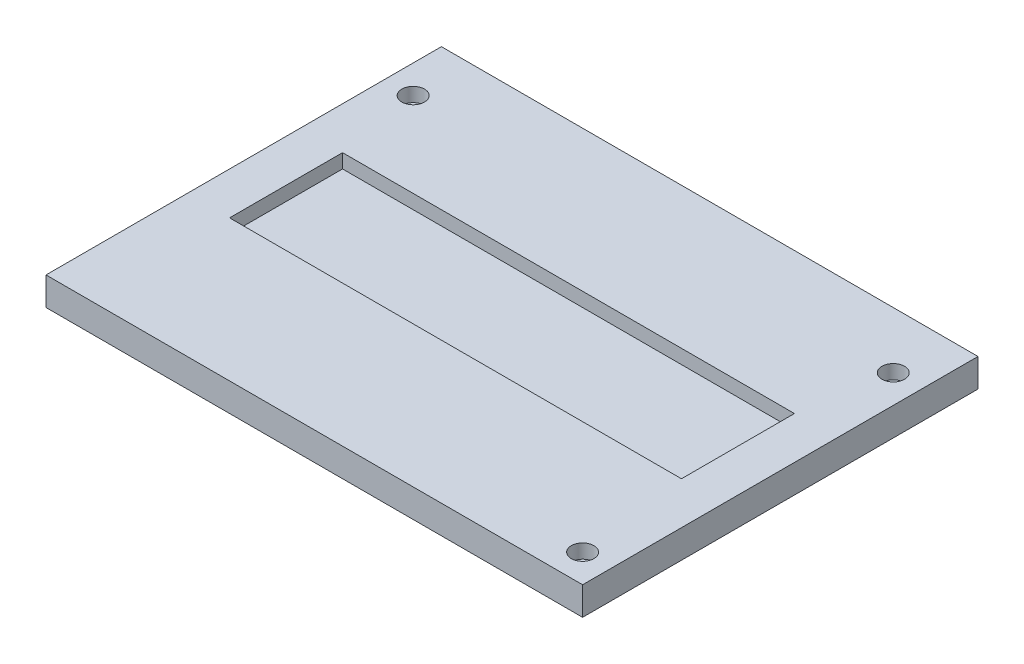
SolidWorks part; units mm, degrees
material "ABS"
ref_plane "Front" through (0, 0, 0) normal (0, 0, 1) x (1, 0, 0)
ref_plane "Top" through (0, 0, 0) normal (0, 1, 0) x (1, 0, 0)
ref_plane "Right" through (0, 0, 0) normal (1, 0, 0) x (0, 0, -1)
sketch "Sketch1" plane through (0, 0, 0) normal (0, 1, 0) x (1, 0, 0)
  line L1 (-60.325, 44.45) -> (60.325, 44.45)
  line L2 (-60.325, 44.45) -> (-60.325, -44.45)
  line L3 (-60.325, -44.45) -> (60.325, -44.45)
  line L4 (60.325, 44.45) -> (60.325, -44.45)
  line L5 (-60.325, 44.45) -> (60.325, -44.45) construction
  line L6 (-60.325, -44.45) -> (60.325, 44.45) construction
  point P0 (0, 0)
  dimension "D1" = 120.65
  dimension "D2" = 88.9
extrude "Boss-Extrude1" add sketch "Sketch1" along normal blind 6.35
sketch "Sketch7" plane through (0, 6.35, 0) normal (0, 1, 0) x (1, 0, 0)
  line L0 (60.325, 44.45) -> (-60.325, 44.45) construction
  line L1 (-60.325, 44.45) -> (-60.325, -44.45) construction
  line L2 (60.325, -44.45) -> (60.325, 44.45) construction
  line L3 (-60.325, -44.45) -> (60.325, -44.45) construction
  circle A0 centre (-53.975, 31.75) radius 2.54
  circle A1 centre (53.975, 31.75) radius 2.54
  circle A2 centre (53.975, -38.1) radius 2.54
  point P12 (0, 0)
  point P15 (0, 0)
  dimension "D5" = 5.08
  dimension "D1" = 12.7
  dimension "D2" = 6.35
  dimension "D3" = 6.35
  dimension "D4" = 6.35
extrude "Cut-Extrude1" cut sketch "Sketch7" against normal offset from surface (3.175 mm away) 3.175 up to face at (0, 0, 0)
hole_wizard "#2 Clearance Hole2" positions "Sketch8" profile "Sketch10" hole size "#2" standard "ANSI Inch" end condition through all
sketch "Sketch8" plane through (0, 3.175, 0) normal (0, 1, 0) x (1, 0, 0)
  point P0 (-53.975, 31.75)
  point P3 (53.975, 31.75)
  point P6 (53.975, -38.1)
sketch "Sketch10" plane through (-53.975, 3.175, -31.75) normal (1, 0, 0) x (0, 0, 1)
  line L0 (0, 0) -> (0, 3.175)
  line L1 (0, 3.175) -> (1.0795, 3.175)
  line L2 (1.0795, 3.175) -> (1.0795, 0.8275)
  line L3 (1.0795, 0.8275) -> (1.7145, 0)
  line L5 (1.7145, 0) -> (0, 0)
  line L6 (-1.0795, 0.8275) -> (-1.7145, 0) construction
  line L11 (0, -6.35) -> (0, 107.95) construction
  dimension "Thru Hole Dia." = 2.159
  dimension "Thru Hole Depth" = 3.175
  dimension "Near C'Sink Dia." = 3.429
  dimension "Near C'Sink Angle" = 75
sketch "Sketch11" plane through (0, 6.35, 0) normal (0, 1, 0) x (1, 0, 0)
  line L1 (-50.8, 12.7) -> (50.8, 12.7)
  line L2 (-50.8, 12.7) -> (-50.8, -12.7)
  line L3 (-50.8, -12.7) -> (50.8, -12.7)
  line L4 (50.8, 12.7) -> (50.8, -12.7)
  line L5 (-50.8, 12.7) -> (50.8, -12.7) construction
  line L6 (-50.8, -12.7) -> (50.8, 12.7) construction
  point P0 (0, 0)
  point P5 (0, 0)
  point P7 (0, 0)
  point P8 (0, 0)
  dimension "D1" = 25.4
  dimension "D2" = 101.6
extrude "Cut-Extrude2" cut sketch "Sketch11" against normal blind 3.175
